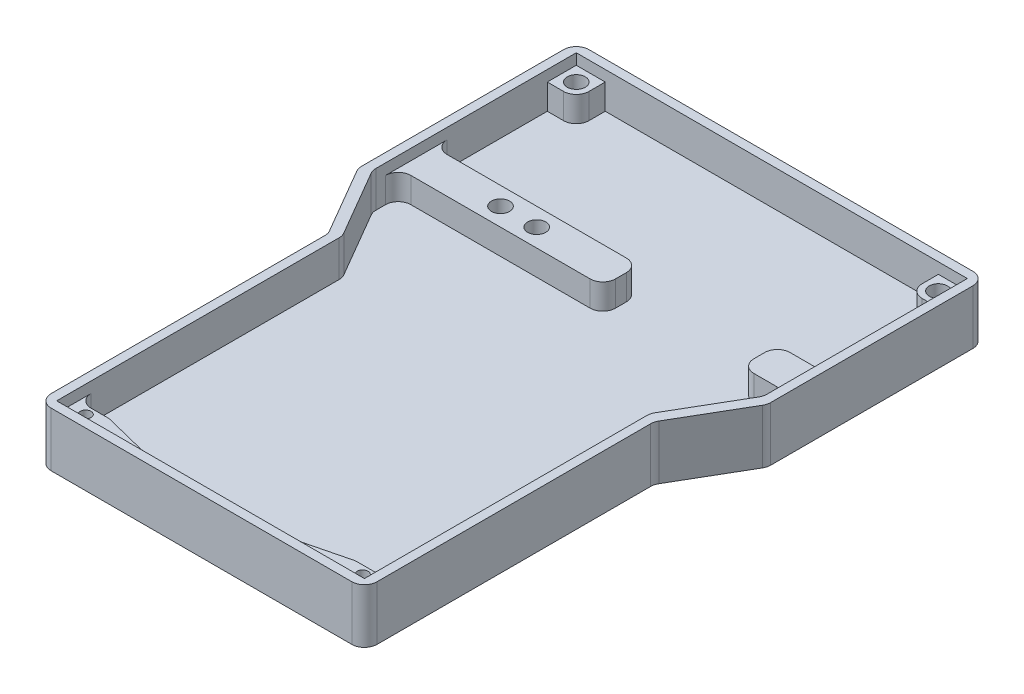
SolidWorks part; units mm, degrees
ref_plane "Front Plane" through (0, 0, 0) normal (0, 0, 1) x (1, 0, 0)
ref_plane "Top Plane" through (0, 0, 0) normal (0, 1, 0) x (1, 0, 0)
ref_plane "Right Plane" through (0, 0, 0) normal (1, 0, 0) x (0, 0, -1)
sketch "Sketch1" plane through (0, 0, 0) normal (0, 1, 0) x (1, 0, 0)
  line L0 (-57.5973, -8.4441) -> (-46.0973, -28.1941)
  line L1 (-46.0973, 51.8059) -> (43.9027, 51.8059)
  line L2 (-46.0973, 51.8059) -> (-46.0973, -108.1941)
  line L3 (-46.0973, -108.1941) -> (43.9027, -108.1941)
  line L4 (43.9027, 51.8059) -> (43.9027, -108.1941)
  line L5 (-57.5973, 51.8059) -> (55.4027, 51.8059)
  line L6 (-57.5973, 51.8059) -> (-57.5973, -8.4441)
  line L7 (-57.5973, -8.4441) -> (55.4027, -8.4441)
  line L8 (55.4027, 51.8059) -> (55.4027, -8.4441)
  line L9 (-57.5973, -8.4441) -> (-46.0973, -8.4441)
  line L10 (-46.0973, -8.4441) -> (-46.0973, -28.1941)
  line L11 (43.9027, -28.1941) -> (43.9027, -8.4441)
  line L12 (43.9027, -8.4441) -> (55.4027, -8.4441)
  line L13 (43.9027, -28.1941) -> (55.4027, -8.4441)
  point P12 (-1.0973, 51.8059)
  point P13 (-1.0973, 51.8059)
  dimension "D1" = 90
  dimension "D2" = 160
  dimension "D3" = 99.75
  dimension "D4" = 113
extrude "Boss-Extrude1" add sketch "Sketch1" along normal blind 5 contours L8 L5 L4 L7 | L2 L7 L4 L1 | L6 L7 L2 L5 | L7 L0 L2 | L7 L2 L3 L4 | L4 L13 L7 | L6 L5 L8 L7 | L12 L11 L13 region at (-49.9306, 0, 15.0275) region at (-51.8473, 0, -21.6809) region at (-1.0973, 0, 58.3191) region at (-1.0973, 0, -21.6809) region at (47.736, 0, 15.0275) region at (49.6527, 0, -21.6809)
sketch "Sketch2" plane through (0, 5, 0) normal (0, 1, 0) x (1, 0, 0)
  line L0 (-46.0973, -108.1941) -> (43.9027, -108.1941)
  line L9 (43.9027, -108.1941) -> (43.9027, -28.1941)
  line L10 (43.9027, -28.1941) -> (55.4027, -8.4441)
  line L11 (55.4027, -8.4441) -> (55.4027, 51.8059)
  line L12 (55.4027, 51.8059) -> (-57.5973, 51.8059)
  line L13 (-57.5973, 51.8059) -> (-57.5973, -8.4441)
  line L14 (-57.5973, -8.4441) -> (-46.0973, -28.1941)
  line L15 (-46.0973, -28.1941) -> (-46.0973, -108.1941)
  line L16 (-43.5973, -105.6941) -> (41.4027, -105.6941)
  line L17 (41.4027, -105.6941) -> (41.4027, -26.7384)
  line L18 (41.4027, -26.7384) -> (52.9027, -6.9884)
  line L19 (52.9027, -6.9884) -> (52.9027, 49.3059)
  line L20 (52.9027, 49.3059) -> (-55.0973, 49.3059)
  line L21 (-55.0973, 49.3059) -> (-55.0973, -6.9884)
  line L22 (-55.0973, -6.9884) -> (-43.5973, -26.7384)
  line L23 (-43.5973, -26.7384) -> (-43.5973, -105.6941)
  line L24 (43.9027, -28.1941) -> (41.4027, -28.1941)
  line L25 (41.4027, -28.1941) -> (41.4027, -26.7384)
  line L26 (43.9027, -28.1941) -> (41.4027, -26.7384)
  line L27 (52.9027, -6.9884) -> (55.4027, -6.9884)
  line L28 (55.4027, -6.9884) -> (55.4027, -8.4441)
  line L29 (52.9027, -6.9884) -> (55.4027, -8.4441)
  line L30 (55.4027, -6.9884) -> (55.4027, -8.4441)
  line L31 (-55.0973, -6.9884) -> (-57.5973, -6.9884)
  line L32 (-57.5973, -6.9884) -> (-57.5973, -8.4441)
  line L33 (-57.5973, -8.4441) -> (-55.0973, -6.9884)
  line L34 (-43.5973, -26.7384) -> (-46.0973, -28.1941)
  line L35 (-46.0973, -28.1941) -> (-43.5973, -28.1941)
  line L36 (-43.5973, -28.1941) -> (-43.5973, -26.7384)
  line L37 (-57.5973, -6.9884) -> (-57.5973, -8.4441)
  dimension "D1" = 2.5
  dimension "D2" = 2.5
  dimension "D3" = 2.5
  dimension "D4" = 90
  dimension "D5" = 90
  dimension "D6" = 2.5
  dimension "D7" = 2.5
  dimension "D8" = 90
  dimension "D9" = 90
extrude "Boss-Extrude2" add sketch "Sketch2" along normal blind 10 contours L35 L15 L0 L9 L24 L17 L16 L23 | L29 L18 L26 L10 | L24 L26 L17 | L27 L29 L11 | L31 L21 L20 L19 L27 L11 L12 L13 | L34 L35 L23 | L34 L22 L33 L14 | L13 L33 L31 region at (-44.8932, 5, 68.1941) region at (-50.5973, 5, 17.5913) region at (-44.4306, 5, 27.7089) region at (48.4027, 5, 17.5913) region at (42.236, 5, 27.7089) region at (-56.764, 5, 7.4737) region at (54.5694, 5, 7.4737) region at (-56.3235, 5, -22.4087)
sketch "Sketch3" plane through (0, 5, 0) normal (0, 1, 0) x (1, 0, 0)
  line L0 (41.4027, -105.6941) -> (41.4027, 49.3059) construction
  line L1 (-43.5973, -105.6941) -> (41.4027, -105.6941)
  line L2 (-43.5973, -105.6941) -> (-43.5973, -99.6941)
  line L3 (-43.5973, -99.6941) -> (41.4027, -99.6941)
  line L4 (41.4027, -105.6941) -> (41.4027, -99.6941)
  line L5 (-35.0973, -99.6941) -> (-23.0973, -102.6941)
  line L6 (-23.0973, -102.6941) -> (20.9027, -102.6941)
  line L7 (20.9027, -102.6941) -> (32.9027, -99.6941)
  line L8 (-35.0973, -99.6941) -> (-35.0973, -105.6941)
  line L9 (-35.0973, -105.6941) -> (32.9027, -105.6941)
  line L10 (32.9027, -105.6941) -> (32.9027, -99.6941)
  line L12 (-55.0973, 49.3059) -> (-47.0973, 49.3059)
  line L13 (-55.0973, 49.3059) -> (-55.0973, 41.3059)
  line L14 (-55.0973, 41.3059) -> (-47.0973, 41.3059)
  line L15 (-47.0973, 49.3059) -> (-47.0973, 41.3059)
  line L16 (52.9027, 49.3059) -> (44.9027, 49.3059)
  line L17 (52.9027, 49.3059) -> (52.9027, 41.3059)
  line L18 (52.9027, 41.3059) -> (44.9027, 41.3059)
  line L19 (44.9027, 49.3059) -> (44.9027, 41.3059)
  circle A0 centre (-39.3473, -101.9441) radius 1.5
  circle A1 centre (37.1527, -101.9441) radius 1.5
  circle A2 centre (-51.0973, 45.3059) radius 2.5
  circle A3 centre (48.9027, 45.3059) radius 2.5
  point P31 (0, 0)
  point P32 (-55.0973, 45.3059)
  point P33 (-51.0973, 41.3059)
  point P34 (48.9027, 41.3059)
  point P35 (44.9027, 45.3059)
  dimension "D4" = 3
  dimension "D7" = 3
  dimension "D17" = 5
  dimension "D18" = 5
  dimension "D1" = 6
  dimension "D2" = 4.25
  dimension "D3" = 3.75
  dimension "D5" = 76.5
  dimension "D6" = 4.25
  dimension "D8" = 12
  dimension "D9" = 12
  dimension "D10" = 3
  dimension "D11" = 8.5
  dimension "D12" = 8.5
  dimension "D13" = 8
  dimension "D14" = 8
  dimension "D15" = 8
  dimension "D16" = 8
extrude "Boss-Extrude3" add sketch "Sketch3" along normal blind 7 contours L8 L3 A0 | L1 L10 L7 L6 L5 L8 | L10 L3 A1 | L13 L12 L15 L14 | L17 L16 L19 L18 | A2 | A3 region at (-43.4933, 5, 102.6941) region at (-1.0973, 5, 103.8191) region at (33.0067, 5, 102.6941)
sketch "Sketch4" plane through (0, 5, 0) normal (0, 1, 0) x (1, 0, 0)
  line L0 (-43.5973, 49.3059) -> (-43.5973, -99.6941) construction
  line L1 (-43.5973, 10.1309) -> (1.4027, 10.1309)
  line L2 (-43.5973, 10.1309) -> (-43.5973, 0.1309)
  line L3 (-43.5973, 0.1309) -> (1.4027, 0.1309)
  line L4 (1.4027, 10.1309) -> (1.4027, 0.1309)
  line L5 (41.4027, 49.3059) -> (-43.5973, 49.3059) construction
  line L6 (41.4027, -99.6941) -> (41.4027, 49.3059) construction
  line L7 (1.4027, 10.1309) -> (-43.5973, 10.1309)
  line L8 (1.4027, 10.1309) -> (1.4027, 49.3059)
  line L9 (1.4027, 49.3059) -> (-43.5973, 49.3059)
  line L10 (-43.5973, 10.1309) -> (-43.5973, 49.3059)
  line L11 (39.6145, 10.1309) -> (41.4027, 10.1309)
  line L12 (39.6145, 10.1309) -> (39.6145, 0.1309)
  line L13 (39.6145, 0.1309) -> (41.4027, 0.1309)
  line L14 (41.4027, 10.1309) -> (41.4027, 0.1309)
  line L15 (-55.0973, 49.3059) -> (-55.0973, -6.9884) construction
  line L16 (-43.5973, 0.1309) -> (-55.0973, 0.1309)
  line L17 (-43.5973, 0.1309) -> (-43.5973, 10.1309)
  line L18 (-43.5973, 10.1309) -> (-55.0973, 10.1309)
  line L19 (-55.0973, 0.1309) -> (-55.0973, 10.1309)
  line L20 (52.9027, -6.9884) -> (52.9027, 49.3059) construction
  line L21 (41.4027, 10.1309) -> (52.9027, 10.1309)
  line L22 (41.4027, 10.1309) -> (41.4027, 0.1309)
  line L23 (41.4027, 0.1309) -> (52.9027, 0.1309)
  line L24 (52.9027, 10.1309) -> (52.9027, 0.1309)
  circle A0 centre (-31.8473, 5.1309) radius 2.5
  circle A1 centre (-21.8473, 5.1309) radius 2.5
  dimension "D3" = 5
  dimension "D4" = 5
  dimension "D1" = 11.75
  dimension "D2" = 21.75
  dimension "D5" = 10
  dimension "D6" = 5
  dimension "D7" = 5
  dimension "D8" = 44.175
  dimension "D9" = 45
extrude "Boss-Extrude4" add sketch "Sketch4" along normal up to surface (7 mm away) contours L4 L1 L3 A1 A0 | L12 L11 L14 L13 | L17 L16 L19 L18 | L22 L21 L24 L23 region at (-21.0973, 5, -9.6699) up to face at (-39.3473, 12, 103.4441)
fillet "Fillet1" radius 3.5 28 edges at (43.9027, 7.5, 108.1941) (-46.0973, 7.5, 108.1941) (52.9027, 8.5, -10.1309) (52.9027, 8.5, -0.1309) (-55.0973, 8.5, -10.1309) (-55.0973, 8.5, -0.1309) (41.4027, 8.5, 99.6941) (-43.5973, 8.5, 99.6941) (-35.0973, 8.5, 99.6941) (-23.0973, 8.5, 102.6941) (32.9027, 8.5, 99.6941) (20.9027, 8.5, 102.6941) (52.9027, 10, 6.9884) (41.4027, 10, 26.7384) (-43.5973, 10, 26.7384) (-55.0973, 10, 6.9884) (39.6145, 8.5, -10.1309) (39.6145, 8.5, -0.1309) (1.4027, 8.5, -10.1309) (1.4027, 8.5, -0.1309) (44.9027, 8.5, -41.3059) (-47.0973, 8.5, -41.3059) (43.9027, 7.5, 28.1941) (55.4027, 7.5, 8.4441) (55.4027, 7.5, -51.8059) (-57.5973, 7.5, -51.8059) (-57.5973, 7.5, 8.4441) (-46.0973, 7.5, 28.1941)
sketch "Sketch5" plane through (0, 5, 0) normal (0, 1, 0) x (1, 0, 0)
  circle A0 centre (-21.8473, 5.1309) radius 2.5
  circle A1 centre (-31.8473, 5.1309) radius 2.5593
  circle A2 centre (-39.3473, -101.9441) radius 1.5
  circle A3 centre (37.1527, -101.9441) radius 1.5
  circle A4 centre (-51.0973, 45.3059) radius 2.5
  circle A5 centre (48.9027, 45.3059) radius 2.5
extrude "Cut-Extrude1" cut sketch "Sketch5" against normal through all
